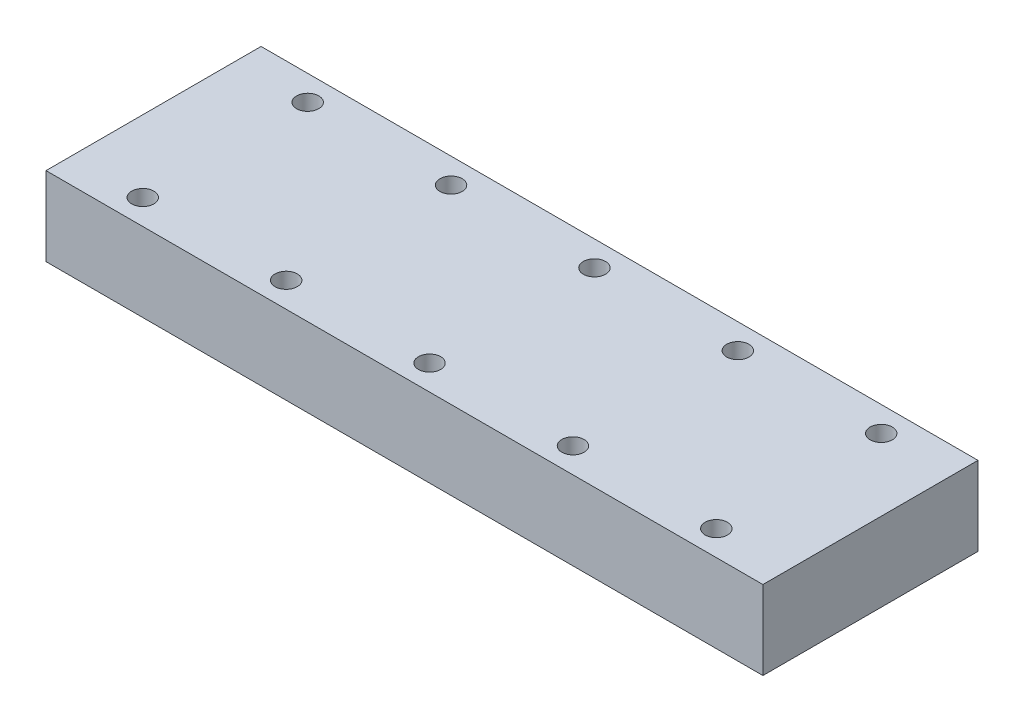
SolidWorks part; units mm, degrees
ref_plane "Front Plane" through (0, 0, 0) normal (0, 0, 1) x (1, 0, 0)
ref_plane "Top Plane" through (0, 0, 0) normal (0, 1, 0) x (1, 0, 0)
ref_plane "Right Plane" through (0, 0, 0) normal (1, 0, 0) x (0, 0, -1)
sketch "Sketch1" plane through (0, 0, 0) normal (0, 1, 0) x (1, 0, 0)
  line L0 (-55, 0) -> (-55, 30)
  line L1 (-55, 30) -> (45, 30)
  line L2 (45, 30) -> (45, 0)
  line L3 (45, 0) -> (-55, 0)
  dimension "D1" = 100
  dimension "D2" = 30
  dimension "D3" = 0
  dimension "D4" = 55
extrude "Boss-Extrude1" add sketch "Sketch1" along normal blind 11
sketch "Sketch4" plane through (0, 0, 0) normal (0, 1, 0) x (1, 0, 0)
  line L0 (-35, 6) -> (-50, 6)
  line L1 (-50, 6) -> (-50, 24)
  line L2 (-50, 24) -> (-20, 24)
  line L3 (-20, 24) -> (-20, 6)
  line L4 (-20, 6) -> (-35, 6)
  line L5 (-55, 30) -> (-55, 0) construction
  line L9 (45, 30) -> (-55, 30) construction
  line L10 (-55, 0) -> (45, 0) construction
  dimension "D1" = 18
  dimension "D2" = 6
  dimension "D3" = 5
  dimension "D4" = 30
  dimension "D5" = 6
extrude "Cut-Extrude1" cut sketch "Sketch4" against normal blind 8 and the other way blind 10.11
sketch "Sketch3" plane through (0, 0, 0) normal (0, 1, 0) x (1, 0, 0)
  line L0 (45, 15) -> (-55, 15) construction
  line L1 (45, 0) -> (45, 30) construction
  line L2 (-55, 30) -> (-55, 0) construction
  line L3 (40, 15) -> (40, 8.41)
  line L4 (40, 8.41) -> (-40, 6.89)
  line L5 (-40, 6.89) -> (-40, 15)
  line L6 (-40, 15) -> (40, 15)
  line L7 (-20, 6) -> (-20, 24) construction
  dimension "D1" = 6.59
  dimension "D2" = 8.11
  dimension "D3" = 80
  dimension "D4" = 20
revolve "Cut-Revolve1" cut sketch "Sketch3" angle 360 about L0
sketch "Sketch5" plane through (0, 0, 0) normal (0, 1, 0) x (1, 0, 0)
  line L0 (30, 8.22) -> (30, 10.72)
  line L1 (-20, 7.27) -> (40, 8.41) construction
  line L2 (30, 10.72) -> (17.5, 10.4825)
  line L3 (17.5, 10.4825) -> (17.5, 7.9825)
  line L4 (17.5, 7.9825) -> (30, 8.22)
  line L5 (40, 15) -> (-16.9672, 15) construction
  line L6 (40, 8.41) -> (40, 21.59) construction
  dimension "D1" = 2.5
  dimension "D2" = 2.5
  dimension "D3" = 12.5
  dimension "D4" = 10
revolve "Revolve1" add sketch "Sketch5" angle 45 about L5 other way angle 225
sketch "Sketch6" plane through (0, 0, 0) normal (0, 1, 0) x (1, 0, 0)
  line L0 (5, 7.745) -> (5, 10.245)
  line L1 (-20, 7.27) -> (17.5, 7.9825) construction
  line L2 (5, 10.245) -> (-7.5, 10.0075)
  line L3 (-7.5, 10.0075) -> (-7.5, 7.5075)
  line L4 (-7.5, 7.5075) -> (5, 7.745)
  line L5 (40, 15) -> (-17.599, 15) construction
  line L6 (40, 8.41) -> (40, 21.59) construction
  dimension "D1" = 2.5
  dimension "D2" = 2.5
  dimension "D3" = 12.5
  dimension "D4" = 12.5
revolve "Revolve2" add sketch "Sketch6" angle 45 about L5 other way angle 225
sketch "Sketch7" plane through (0, 0, 0) normal (0, 1, 0) x (1, 0, 0)
  line L0 (45, 0) -> (45, 30)
  line L1 (45, 30) -> (-55, 30)
  line L2 (-55, 30) -> (-55, 0)
  line L3 (-55, 0) -> (45, 0)
extrude "Cut-Extrude2" cut sketch "Sketch7" against normal blind 15
fillet "Fillet1" radius 1.2 20 edges at (17.5, 2.6855, -21.4833) (17.5, 1.7288, -19.1736) (5, 1.8197, -19.393) (5, 1.8197, -10.607) (17.5, 2.6855, -8.5167) (17.5, 1.7288, -10.8264) (5, 2.7764, -8.2973) (5, 2.7764, -21.7027) (30, 2.5946, -8.7361) (30, 2.5946, -21.2639) (23.75, 3.1104, -11.8896) (30, 1.6379, -11.0458) (30, 1.6379, -18.9542) (-7.5, 1.9105, -19.6125) (-7.5, 2.8673, -21.9222) (-7.5, 2.8673, -8.0778) (-7.5, 1.9105, -10.3875) (-1.25, 3.4463, -11.5537) (23.75, 3.1104, -18.1104) (-1.25, 3.4463, -18.4463)
ref_plane "Plane1" through (-55, 0, 0) normal (-1, 0, 0) x (0, 0, 1)
sketch "Sketch9" plane through (0, 0, 0) normal (0, 1, 0) x (1, 0, 0)
  line L0 (45, 0) -> (45, 30) construction
  line L3 (45, 30) -> (-55, 30) construction
  line L4 (45, 15) -> (-55.4355, 15) construction
  line L5 (-55, 0) -> (45, 0) construction
  circle A0 centre (35, 26.5) radius 1.55
  circle A1 centre (15, 26.5) radius 1.55
  circle A2 centre (-5, 26.5) radius 1.55
  circle A3 centre (-25, 26.5) radius 1.55
  circle A4 centre (-45, 26.5) radius 1.55
  circle A5 centre (35, 3.5) radius 1.55
  circle A6 centre (15, 3.5) radius 1.55
  circle A7 centre (-5, 3.5) radius 1.55
  circle A8 centre (-25, 3.5) radius 1.55
  circle A9 centre (-45, 3.5) radius 1.55
  dimension "D6" = 3.1
  dimension "D7" = 3.1
  dimension "D8" = 3.1
  dimension "D9" = 3.1
  dimension "D10" = 3.1
  dimension "D21" = 3.1
  dimension "D22" = 3.1
  dimension "D23" = 3.1
  dimension "D24" = 3.1
  dimension "D25" = 3.1
  dimension "D1" = 10
  dimension "D2" = 20
  dimension "D3" = 20
  dimension "D4" = 20
  dimension "D5" = 20
  dimension "D11" = 3.5
  dimension "D12" = 3.5
  dimension "D13" = 3.5
  dimension "D14" = 3.5
  dimension "D15" = 3.5
  dimension "D16" = 3.5
  dimension "D17" = 3.5
  dimension "D18" = 3.5
  dimension "D19" = 3.5
  dimension "D20" = 3.5
fillet "Fillet9" radius 1.2 7 edges at (-35, 10.11, -6) (-50, 5.055, -6) (-50, 5.055, -24) (-50, 10.11, -15) (-35, 10.11, -24) (-20, 7.73, -15) (-20, 10.11, -15)
fillet "Fillet10" radius 0.5 4 edges at (-20.3515, 9.7585, -6.3515) (-20.3515, 9.7585, -23.6485) (-20, 4.455, -6) (-20, 4.455, -24)
extrude "Cut-Extrude3" cut sketch "Sketch9" against normal blind 15 and the other way blind 20
sketch "Sketch10" plane through (-55, 0, 0) normal (-1, 0, 0) x (0, 0, 1)
  line L0 (-30, 0) -> (0, 0) construction
  line L1 (-30, 11) -> (-30, 0) construction
  circle A0 centre (-15, 3) radius 2
  dimension "D1" = 4
  dimension "D2" = 3
  dimension "D3" = 15
extrude "Cut-Extrude4" cut sketch "Sketch10" against normal blind 10
